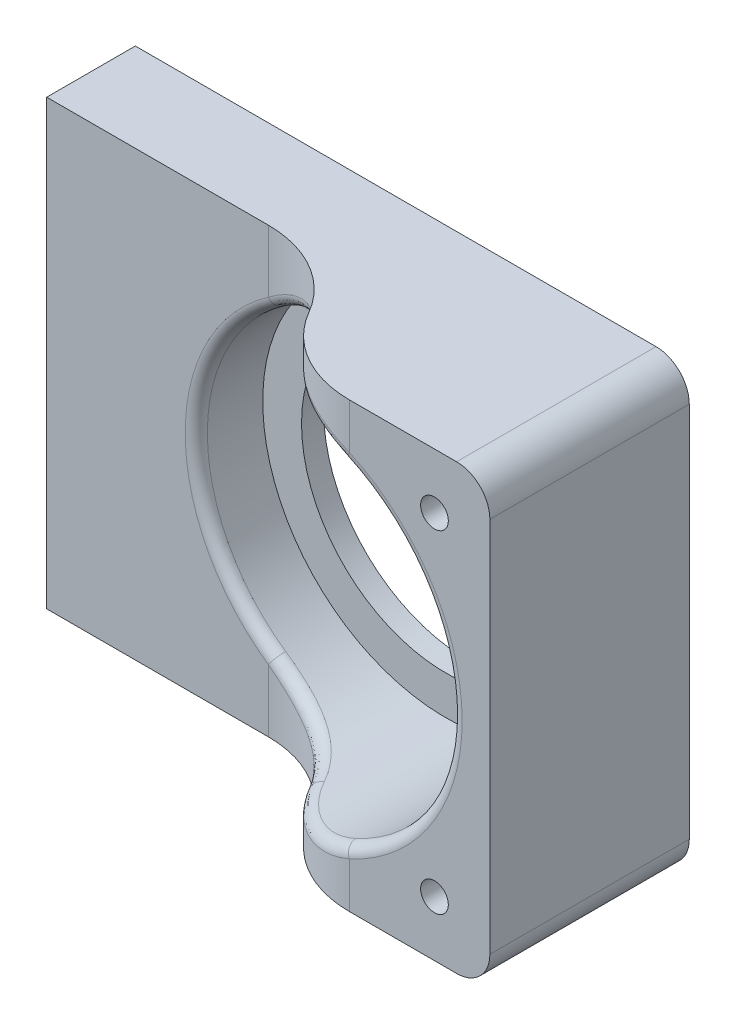
SolidWorks part; units mm, degrees
ref_plane "前视基准面" through (0, 0, 0) normal (0, 0, 1) x (1, 0, 0)
ref_plane "上视基准面" through (0, 0, 0) normal (0, 1, 0) x (1, 0, 0)
ref_plane "右视基准面" through (0, 0, 0) normal (1, 0, 0) x (0, 0, -1)
sketch "草图1" plane through (0, 0, 0) normal (0, 0, 1) x (1, 0, 0)
  line L1 (-25, -20) -> (25, -20)
  line L2 (-25, -20) -> (-25, 20)
  line L3 (-25, 20) -> (25, 20)
  line L4 (25, -20) -> (25, 20)
  line L5 (-25, -20) -> (25, 20) construction
  line L6 (-25, 20) -> (25, -20) construction
  point P0 (0, 0)
  dimension "D1" = 40
  dimension "D2" = 50
extrude "凸台-拉伸1" add sketch "草图1" along normal blind 8
sketch "草图2" plane through (0, 0, 8) normal (0, 0, 1) x (1, 0, 0)
  line L0 (-25, -20) -> (25, -20) construction
  line L1 (25, 20) -> (5, 20)
  line L2 (25, 20) -> (25, -20)
  line L3 (25, -20) -> (5, -20)
  line L4 (5, 20) -> (5, -20)
  dimension "D1" = 20
extrude "凸台-拉伸2" add sketch "草图2" along normal blind 10
sketch "草图3" plane through (0, 0, 18) normal (0, 0, 1) x (1, 0, 0)
  line L0 (-25, 0) -> (25, 0) construction
  line L1 (-25, 20) -> (-25, -20) construction
  line L2 (25, -20) -> (25, 20) construction
  circle A0 centre (5, 0) radius 16.5
  dimension "D2" = 33
  dimension "D1" = 30
extrude "切除-拉伸1" cut sketch "草图3" against normal blind 16
sketch "草图5" plane through (0, 0, 18) normal (0, 0, 1) x (1, 0, 0)
  line L0 (-25, 0) -> (25, 0) construction
  line L1 (-25, 20) -> (-25, -20) construction
  line L2 (25, -20) -> (25, 20) construction
  circle A0 centre (20, 15) radius 1.25
  circle A1 centre (5, 0) radius 16.5 construction
  circle A2 centre (20, -15) radius 1.25
  dimension "D3" = 2.5
  dimension "D1" = 15
  dimension "D2" = 15
extrude "切除-拉伸2" cut sketch "草图5" against normal through all
sketch "草图6" plane through (-25, 0, 0) normal (-1, 0, 0) x (0, 0, 1)
  line L0 (8, 0) -> (0, 0) construction
  line L1 (8, 20) -> (8, -20) construction
  line L2 (0, 20) -> (0, -20) construction
  circle A0 centre (4, 15) radius 1.25
  circle A1 centre (4, -15) radius 1.25
  dimension "D3" = 2.5
  dimension "D1" = 15
  dimension "D2" = 4
extrude "切除-拉伸3" cut sketch "草图6" against normal blind 10
fillet "圆角1" radius 10 2 edges at (5, -18.25, 8) (5, 18.25, 8)
fillet "圆角2" radius 10 2 edges at (5, -18.25, 18) (5, 18.25, 18)
fillet "圆角3" radius 3 2 edges at (25, 20, 9) (25, -20, 9)
sketch "草图7" plane through (0, 0, 2) normal (0, 0, 1) x (1, 0, 0)
  circle A0 centre (5, 0) radius 13
  dimension "D1" = 26
extrude "切除-拉伸4" cut sketch "草图7" against normal through all
fillet "圆角4" radius 1 6 edges at (-2.1973, -14.8475, 8.4008) (8.3922, -16.1475, 17.1961) (21.5, 0, 18) (6.7544, 16.4065, 16.3078) (0.4084, 15.8483, 9.5888) (-11.5, 0, 8)
